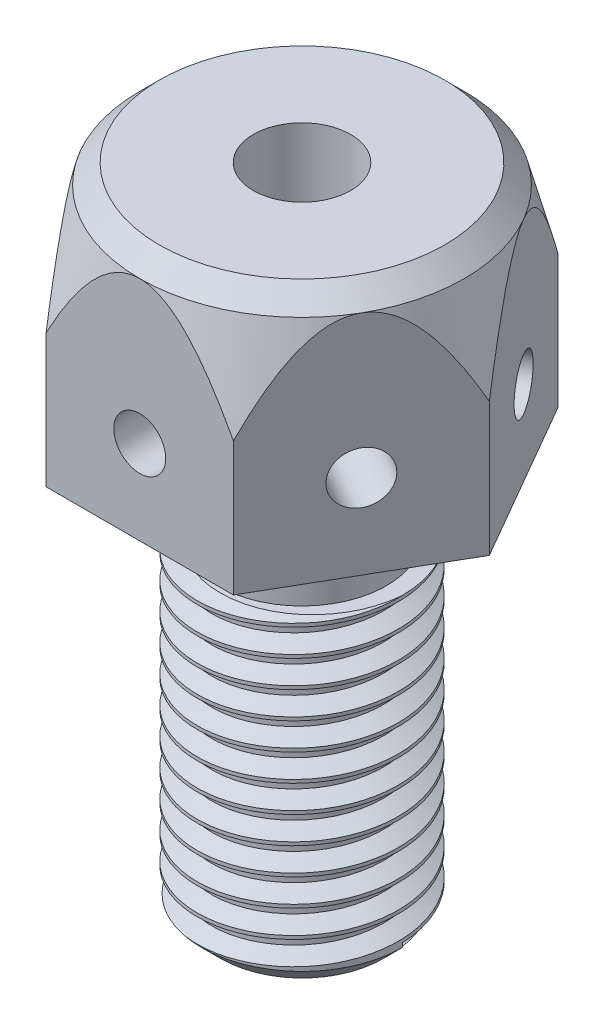
SolidWorks part; units mm, degrees
ref_plane "Front Plane" through (0, 0, 0) normal (0, 0, 1) x (1, 0, 0)
ref_plane "Top Plane" through (0, 0, 0) normal (0, 1, 0) x (1, 0, 0)
ref_plane "Right Plane" through (0, 0, 0) normal (1, 0, 0) x (0, 0, -1)
sketch "Sketch1" plane through (0, 0, 0) normal (0, 1, 0) x (1, 0, 0)
  circle A0 centre (0, 0) radius 3.937
  dimension "D1" = 7.874
extrude "Boss-Extrude1" add sketch "Sketch1" along normal blind 12.7
chamfer "Chamfer1" distance 0.762 angle 45 1 edges at (0, 0, 3.937)
thread "Thread1" pitch 1.0583 method cut profile "Thread Profile1" start angle 0, offset 0, length 12.7, pitch 1.0583, diameter 7.874
ref_plane "Plane1" through (3.937, 0, 0) normal (0, 0, 1) x (1, 0, 0)
sketch "Thread Profile1" plane through (3.937, 0, 0) normal (0, 0, 1) x (1, 0, 0)
  line L0 (0, 0) -> (0, 1.0583) construction
  line L11 (0, 0) -> (0, 0.926)
  line L12 (0, 0.926) -> (-0.5728, 0.5953)
  line L13 (-0.5728, 0.5953) -> (-0.5728, 0.3307)
  line L15 (-0.5728, 0.3307) -> (0, 0)
  line L17 (-0.5728, 0.463) -> (0, 0.463) construction
  point P2 (0, 0)
  dimension "Pitch" = 1.0583
  dimension "Profile_Angle" = 60
  dimension "Profile_Land" = 0.2646
  dimension "Profile_Height" = 0.5728
sketch "Sketch4" plane through (0, 12.7, 0) normal (0, 1, 0) x (1, 0, 0)
  circle A0 centre (0, 0) radius 3.302
  dimension "D1" = 6.604
extrude "Boss-Extrude2" add sketch "Sketch4" along normal blind 3.048
sketch "Sketch5" plane through (0, 15.748, 0) normal (0, 1, 0) x (1, 0, 0)
  line L1 (3.6662, 6.35) -> (-3.6662, 6.35)
  line L2 (-3.6662, 6.35) -> (-7.3323, 0)
  line L3 (-7.3323, 0) -> (-3.6662, -6.35)
  line L4 (-3.6662, -6.35) -> (3.6662, -6.35)
  line L5 (3.6662, -6.35) -> (7.3323, 0)
  line L6 (7.3323, 0) -> (3.6662, 6.35)
  circle A0 centre (0, 0) radius 6.35 construction
  dimension "D1" = 12.7
extrude "Boss-Extrude3" add sketch "Sketch5" along normal blind 8.89
sketch "Sketch6" plane through (0, 24.638, 0) normal (0, 1, 0) x (1, 0, 0)
  line L0 (3.6662, 6.35) -> (-3.6662, 6.35) construction
  circle A0 centre (0, 0) radius 6.35
extrude "Boss-Extrude4" add sketch "Sketch6" along normal blind 0.762
chamfer "Chamfer2" distance 0.762 angle 45 1 edges at (0, 25.4, 6.35)
ref_plane "Plane2" through (0, 0, 0) normal (-0.866, 0, -0.5) x (-0.5, 0, 0.866)
sketch "Sketch7" plane through (0, 0, 0) normal (-0.866, 0, -0.5) x (-0.5, 0, 0.866)
  line L0 (-6.35, 24.638) -> (-7.3323, 24.638)
  line L1 (-7.3323, 24.638) -> (-7.3323, 20.9718)
  line L2 (-7.3323, 20.9718) -> (-6.35, 24.638)
  line L3 (-7.3323, 24.638) -> (-7.3323, 15.748) construction
  dimension "D1" = 75
sweep "Cut-Sweep1" cut profiles "Sketch7" path edge at (0, 15.748, 3.302)
sketch "Sketch9" plane through (5.4993, 0, -3.175) normal (0.866, 0, -0.5) x (-0.5, 0, -0.866)
  line L0 (3.302, 12.7) -> (-3.302, 12.7) construction
  circle A0 centre (0, 19.05) radius 1.016
  dimension "D2" = 2.032
  dimension "D1" = 6.35
extrude "Cut-Extrude1" cut sketch "Sketch9" against normal blind 6.35
pattern_circular "CirPattern1" count 6 over 360 about axis through (0, 15.748, 0) along (0, 1, 0) of "Cut-Extrude1"
sketch "Sketch10" plane through (0, 25.4, 0) normal (0, 1, 0) x (1, 0, 0)
  circle A0 centre (0, 0) radius 1.905
  dimension "D1" = 3.81
extrude "Cut-Extrude2" cut sketch "Sketch10" against normal blind 7.874
